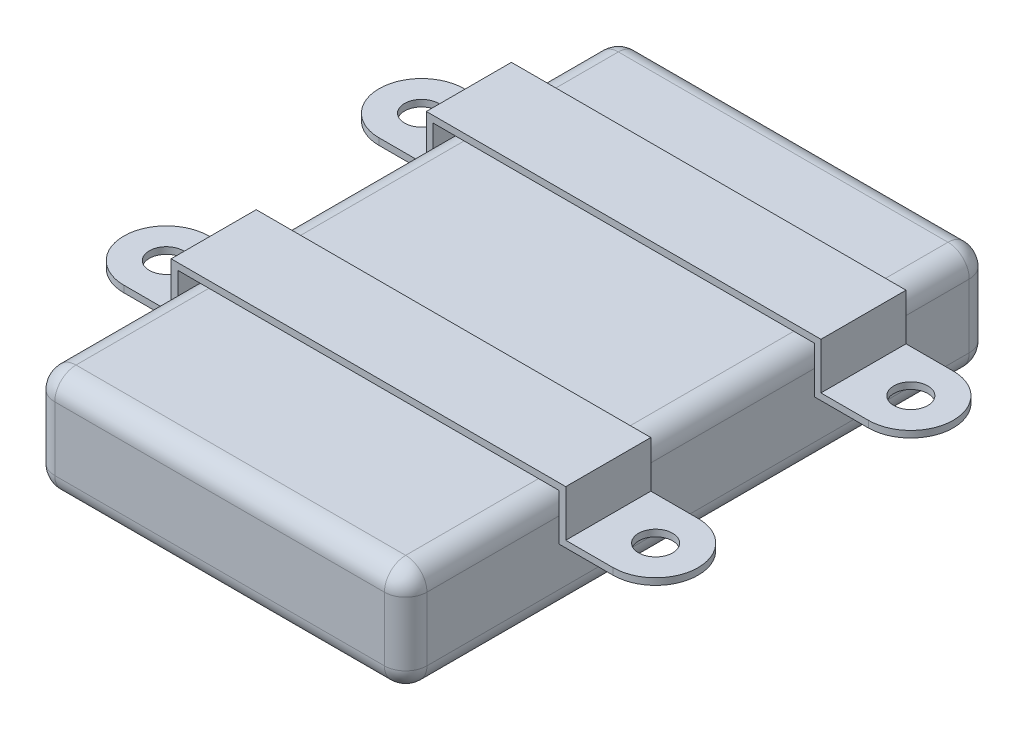
SolidWorks part; units mm, degrees
ref_plane "Front Plane" through (0, 0, 0) normal (0, 0, 1) x (1, 0, 0)
ref_plane "Top Plane" through (0, 0, 0) normal (0, 1, 0) x (1, 0, 0)
ref_plane "Right Plane" through (0, 0, 0) normal (1, 0, 0) x (0, 0, -1)
sketch "Sketch1" plane through (0, 0, 0) normal (1, 0, 0) x (0, 0, -1)
  line L0 (0, 0) -> (0, 12.7)
  line L1 (0, 12.7) -> (69.85, 12.7)
  line L2 (69.85, 12.7) -> (69.85, 0)
  line L3 (69.85, 0) -> (0, 0)
  dimension "D1" = 69.85
  dimension "D2" = 12.7
extrude "Extrude1" add sketch "Sketch1" along normal mid plane 44.45
fillet "Fillet1" radius 2.54 12 edges at (-22.225, 0, -34.925) (0, 0, -69.85) (-22.225, 6.35, -69.85) (22.225, 6.35, -69.85) (22.225, 0, -34.925) (22.225, 6.35, 0) (0, 0, 0) (-22.225, 6.35, 0) (0, 12.7, -69.85) (22.225, 12.7, -34.925) (0, 12.7, 0) (-22.225, 12.7, -34.925)
sketch "Sketch2" plane through (0, 0, 0) normal (0, 0, 1) x (1, 0, 0)
  line L0 (-34.8689, 7.7841) -> (-22.7711, 7.7841)
  line L1 (-22.7711, 7.7841) -> (-22.7711, 13.3337)
  line L2 (-22.7711, 13.3337) -> (0, 13.3337)
  line L3 (0, 22.8298) -> (0, -3.2847) construction
  line L4 (-34.8689, 8.5779) -> (-23.5648, 8.5779)
  line L5 (-23.5648, 8.5779) -> (-23.5648, 14.1274)
  line L6 (-23.5648, 14.1274) -> (0, 14.1274)
  line L7 (-34.8689, 7.7841) -> (-34.8689, 8.5779)
  line L8 (34.8689, 7.7841) -> (34.8689, 8.5779)
  line L9 (23.5648, 14.1274) -> (0, 14.1274)
  line L10 (23.5648, 8.5779) -> (23.5648, 14.1274)
  line L11 (34.8689, 8.5779) -> (23.5648, 8.5779)
  line L12 (22.7711, 13.3337) -> (0, 13.3337)
  line L13 (22.7711, 7.7841) -> (22.7711, 13.3337)
  line L14 (34.8689, 7.7841) -> (22.7711, 7.7841)
  dimension "D1" = 0.7937
extrude "Extrude2" add sketch "Sketch2" along normal blind 10.16 from offset 27.94 separate body offset against normal yes
extrude "Extrude3" add sketch "Sketch2<2>" along normal blind 10.16 from offset 58.42 separate body offset against normal yes
sketch "Sketch2<2>" plane through (0, 0, 0) normal (0, 0, 1) x (1, 0, 0) same geometry as "Sketch2"
sketch "Sketch3" plane through (0, 0, 0) normal (0, 1, 0) x (1, 0, 0)
  line L0 (27.1849, 53.34) -> (34.8689, 53.34) construction
  line L1 (-29.2169, 58.42) -> (-40.1514, 58.42)
  line L2 (34.8689, 48.26) -> (34.8689, 58.42) construction
  line L3 (29.2169, 58.42) -> (29.2169, 17.78) construction
  line L4 (-40.1514, 58.42) -> (-40.1514, 48.26)
  line L5 (-40.1514, 48.26) -> (-29.2169, 48.26)
  line L6 (0, 58.42) -> (0, 17.78) construction
  line L7 (23.5648, 58.42) -> (-23.5648, 58.42) construction
  line L8 (23.5648, 17.78) -> (-23.5648, 17.78) construction
  line L9 (34.8689, 58.42) -> (23.5648, 58.42) construction
  line L10 (34.8689, 17.78) -> (23.5648, 17.78) construction
  line L11 (29.2169, 38.1) -> (-45.7644, 38.1) construction
  line L12 (-29.2169, 17.78) -> (-40.1514, 17.78)
  line L13 (-40.1514, 27.94) -> (-29.2169, 27.94)
  line L14 (-40.1514, 17.78) -> (-40.1514, 27.94)
  line L15 (40.1514, 48.26) -> (29.2169, 48.26)
  line L16 (40.1514, 58.42) -> (40.1514, 48.26)
  line L17 (29.2169, 58.42) -> (40.1514, 58.42)
  line L18 (40.1514, 17.78) -> (40.1514, 27.94)
  line L19 (40.1514, 27.94) -> (29.2169, 27.94)
  line L20 (29.2169, 17.78) -> (40.1514, 17.78)
  circle A0 centre (29.2169, 53.34) radius 2.032
  circle A1 centre (29.2169, 22.86) radius 2.032
  circle A2 centre (-29.2169, 22.86) radius 2.032
  circle A3 centre (-29.2169, 53.34) radius 2.032
  arc A4 (-29.2169, 58.42) -> (-29.2169, 48.26) centre (-29.2169, 53.34) ccw
  arc A5 (-29.2169, 17.78) -> (-29.2169, 27.94) centre (-29.2169, 22.86) cw
  arc A6 (29.2169, 58.42) -> (29.2169, 48.26) centre (29.2169, 53.34) cw
  arc A7 (29.2169, 17.78) -> (29.2169, 27.94) centre (29.2169, 22.86) ccw
  dimension "D1" = 4.064
extrude "Extrude4" cut sketch "Sketch3" along normal blind 18.542
